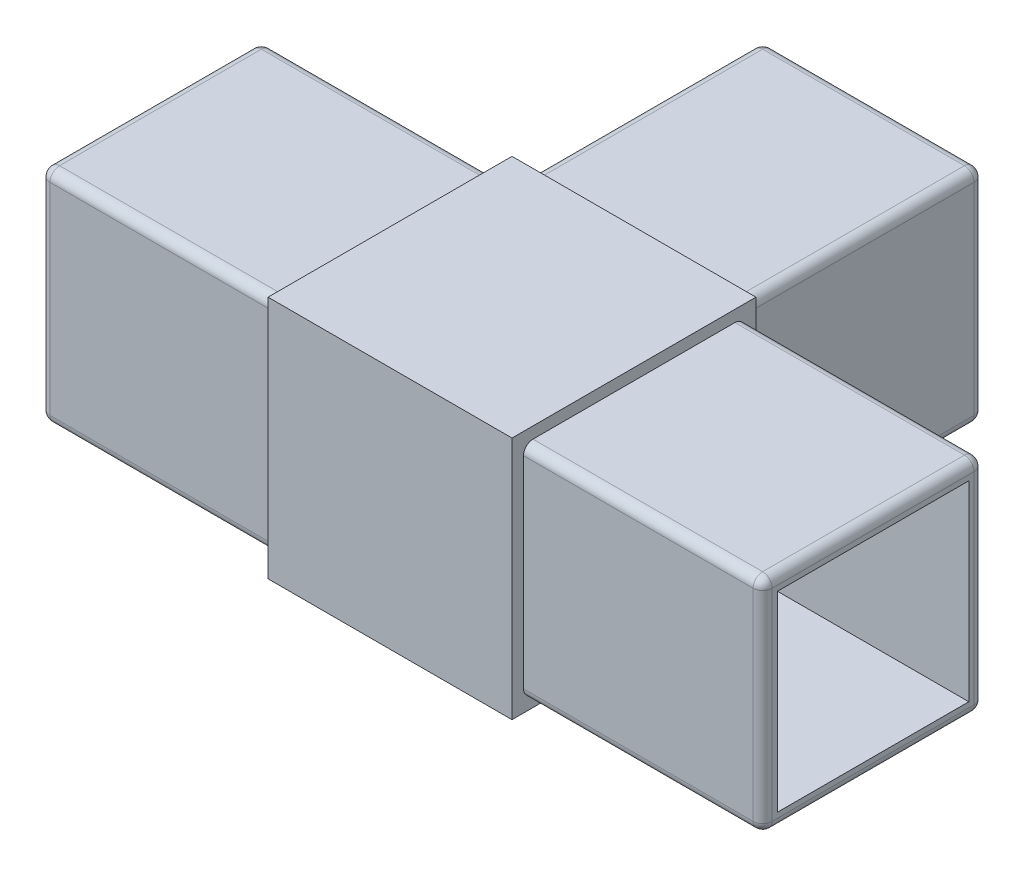
SolidWorks part; units mm, degrees
material "PBT General Purpose"
ref_plane "Front" through (0, 0, 0) normal (0, 0, 1) x (1, 0, 0)
ref_plane "Top" through (0, 0, 0) normal (0, 1, 0) x (1, 0, 0)
ref_plane "Right" through (0, 0, 0) normal (1, 0, 0) x (0, 0, -1)
sketch "Sketch1" plane through (0, 0, 0) normal (0, 1, 0) x (1, 0, 0)
  line L0 (-11.55, 12.75) -> (11.55, 12.75)
  line L1 (-12.75, 12.75) -> (12.75, 12.75)
  line L2 (-12.75, 12.75) -> (-12.75, -12.75)
  line L3 (-12.75, -12.75) -> (12.75, -12.75)
  line L4 (12.75, 12.75) -> (12.75, -12.75)
  line L5 (-12.75, 12.75) -> (12.75, -12.75) construction
  line L6 (-12.75, -12.75) -> (12.75, 12.75) construction
  line L8 (-37.75, 11.55) -> (-37.75, -11.55)
  line L10 (37.75, 11.55) -> (37.75, -11.55)
  line L11 (37.75, 11.55) -> (12.75, 11.55)
  line L12 (12.75, 11.55) -> (12.75, -11.55)
  line L15 (11.55, 37.75) -> (-11.55, 37.75)
  line L17 (12.75, -11.55) -> (37.75, -11.55)
  line L18 (-37.75, -11.55) -> (-12.75, -11.55)
  line L22 (11.55, 12.75) -> (11.55, 37.75)
  line L23 (-11.55, 12.75) -> (-11.55, 37.75)
  line L24 (-12.75, -11.55) -> (-12.75, 11.55)
  line L25 (-12.75, 11.55) -> (-37.75, 11.55)
  line L26 (37.75, 0) -> (-37.75, 0) construction
  line L27 (0, 0) -> (0, 37.75) construction
  point P0 (0, 0)
  point P6 (0, 0)
  point P11 (0, 0)
  point P19 (0, 0)
  point P26 (0, 0)
  point P27 (0, 0)
  dimension "D1" = 25
  dimension "D2" = 25.5
  dimension "D3" = 23.1
extrude "Boss-Extrude2" add sketch "Sketch1" along normal blind 25.5 contours L2 L25 L8 L18 | L4 L1 L0 L2 L3 | L23 L0 L22 L15 | L4 L17 L10 L11 region at (0, 0, -25.25) region at (0, 0, 0) region at (-25.25, 0, 0) region at (25.25, 0, 0)
sketch "Sketch2" plane through (37.75, 0, 0) normal (1, 0, 0) x (0, 0, -1)
  line L0 (11.55, 25.5) -> (11.55, 0) construction
  line L1 (-11.55, 25.5) -> (11.55, 25.5)
  line L2 (-11.55, 25.5) -> (-11.55, 24.3)
  line L3 (-11.55, 24.3) -> (11.55, 24.3)
  line L4 (11.55, 25.5) -> (11.55, 24.3)
  line L5 (-11.55, 25.5) -> (-11.55, 0) construction
  line L6 (11.55, 0) -> (-11.55, 0)
  line L7 (11.55, 0) -> (11.55, 1.2)
  line L8 (11.55, 1.2) -> (-11.55, 1.2)
  line L9 (-11.55, 0) -> (-11.55, 1.2)
  dimension "D1" = 1.2
extrude "Cut-Extrude1" cut sketch "Sketch2" against normal blind 25
sketch "Sketch3" plane through (-37.75, 0, 0) normal (-1, 0, 0) x (0, 0, 1)
  line L0 (11.55, 25.5) -> (11.55, 0) construction
  line L1 (-11.55, 25.5) -> (11.55, 25.5)
  line L2 (-11.55, 25.5) -> (-11.55, 24.3)
  line L3 (-11.55, 24.3) -> (11.55, 24.3)
  line L4 (11.55, 25.5) -> (11.55, 24.3)
  line L5 (-11.55, 25.5) -> (-11.55, 0) construction
  line L6 (11.55, 0) -> (-11.55, 0)
  line L7 (11.55, 0) -> (11.55, 1.2)
  line L8 (11.55, 1.2) -> (-11.55, 1.2)
  line L9 (-11.55, 0) -> (-11.55, 1.2)
  dimension "D1" = 1.2
extrude "Cut-Extrude2" cut sketch "Sketch3" against normal blind 25
sketch "Sketch4" plane through (0, 0, -37.75) normal (0, 0, -1) x (-1, 0, 0)
  line L0 (11.55, 25.5) -> (11.55, 0) construction
  line L1 (-11.55, 25.5) -> (11.55, 25.5)
  line L2 (-11.55, 25.5) -> (-11.55, 24.3)
  line L3 (-11.55, 24.3) -> (11.55, 24.3)
  line L4 (11.55, 25.5) -> (11.55, 24.3)
  line L5 (-11.55, 25.5) -> (-11.55, 0) construction
  line L6 (11.55, 0) -> (-11.55, 0)
  line L7 (11.55, 0) -> (11.55, 1.2)
  line L8 (11.55, 1.2) -> (-11.55, 1.2)
  line L9 (-11.55, 0) -> (-11.55, 1.2)
  dimension "D1" = 1.2
extrude "Cut-Extrude3" cut sketch "Sketch4" against normal blind 25
sketch "Sketch5" plane through (37.75, 0, 0) normal (1, 0, 0) x (0, 0, -1)
  line L0 (-11.55, 24.3) -> (11.55, 1.2) construction
  line L2 (-10, 22.75) -> (10, 22.75)
  line L3 (-10, 22.75) -> (-10, 2.75)
  line L4 (-10, 2.75) -> (10, 2.75)
  line L5 (10, 22.75) -> (10, 2.75)
  line L6 (-10, 22.75) -> (10, 2.75) construction
  line L7 (-10, 2.75) -> (10, 22.75) construction
  point P4 (0, 12.75)
  dimension "D1" = 20
extrude "Cut-Extrude4" cut sketch "Sketch5" against normal through all
sketch "Sketch8" plane through (0, 0, -37.75) normal (0, 0, -1) x (-1, 0, 0)
  line L0 (-11.55, 24.3) -> (11.55, 1.2) construction
  line L2 (-10, 22.75) -> (10, 22.75)
  line L3 (-10, 22.75) -> (-10, 2.75)
  line L4 (-10, 2.75) -> (10, 2.75)
  line L5 (10, 22.75) -> (10, 2.75)
  line L6 (-10, 22.75) -> (10, 2.75) construction
  line L7 (-10, 2.75) -> (10, 22.75) construction
  point P4 (0, 12.75)
  dimension "D1" = 20
extrude "Cut-Extrude5" cut sketch "Sketch8" against normal blind 30
fillet "Fillet1" radius 1 24 edges at (37.75, 1.2, 0) (37.75, 12.75, 11.55) (37.75, 24.3, 0) (37.75, 12.75, -11.55) (25.25, 1.2, 11.55) (25.25, 1.2, -11.55) (25.25, 24.3, 11.55) (25.25, 24.3, -11.55) (0, 1.2, -37.75) (11.55, 12.75, -37.75) (0, 24.3, -37.75) (-11.55, 12.75, -37.75) (11.55, 1.2, -25.25) (-11.55, 1.2, -25.25) (11.55, 24.3, -25.25) (-11.55, 24.3, -25.25) (-37.75, 1.2, 0) (-37.75, 24.3, 0) (-37.75, 12.75, 11.55) (-37.75, 12.75, -11.55) (-25.25, 1.2, -11.55) (-25.25, 1.2, 11.55) (-25.25, 24.3, 11.55) (-25.25, 24.3, -11.55)
